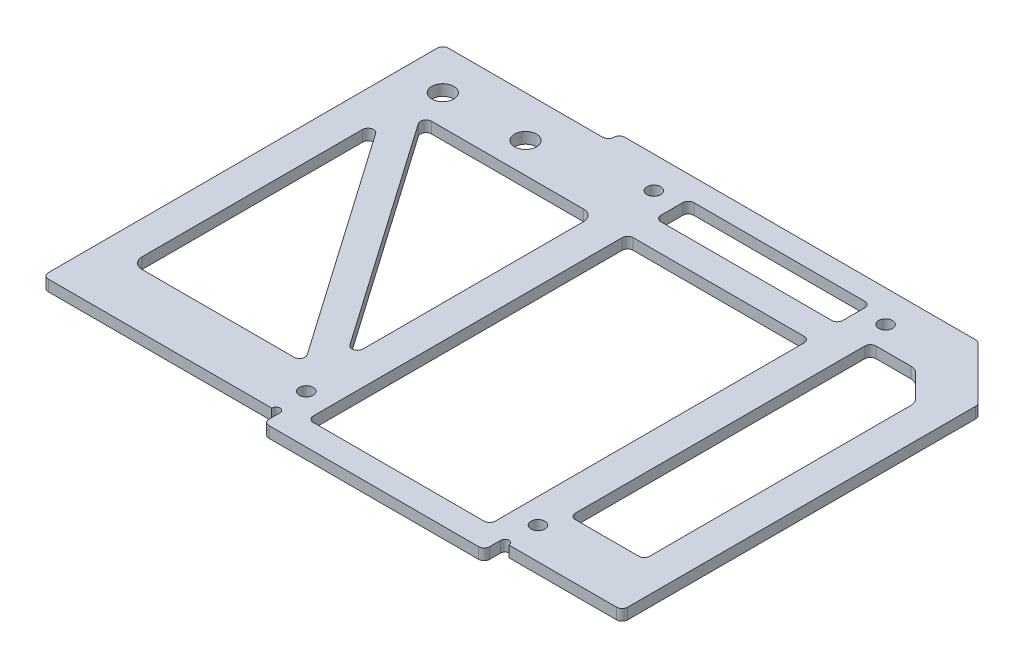
SolidWorks part; units mm, degrees
material "Thornel Mat VMA"
ref_plane "前视基准面" through (0, 0, 0) normal (0, 0, 1) x (1, 0, 0)
ref_plane "上视基准面" through (0, 0, 0) normal (0, 1, 0) x (1, 0, 0)
ref_plane "右视基准面" through (0, 0, 0) normal (1, 0, 0) x (0, 0, -1)
sketch "草图1" plane through (0, 0, 0) normal (0, 1, 0) x (1, 0, 0)
  line L0 (7.5, -7.5) -> (22.5, -7.5) construction
  line L1 (0, 0) -> (30, 0)
  line L2 (0, 0) -> (0, -72.5)
  line L3 (0, -72.5) -> (43, -72.5)
  line L4 (105, -8) -> (105, -72.5)
  line L5 (83, -72.5) -> (105, -72.5)
  line L6 (15, -28) -> (43, -28) construction
  line L11 (30, 0) -> (30, 2)
  line L12 (30, 2) -> (95, 2)
  line L15 (43, -72.5) -> (43, -75.5)
  line L16 (43, -75.5) -> (83, -75.5)
  line L17 (83, -72.5) -> (83, -75.5)
  line L18 (95, 2) -> (105, -8)
  line L19 (42, -3.75) -> (84, -3.75) construction
  line L20 (42, -3.75) -> (42, -66.75) construction
  line L21 (42, -66.75) -> (84, -66.75) construction
  line L22 (84, -3.75) -> (84, -66.75) construction
  line L23 (63, -66.75) -> (63, -75.5) construction
  circle A0 centre (7.5, -7.5) radius 2
  circle A1 centre (22.5, -7.5) radius 2
  circle A2 centre (15, -28) radius 1.5 construction
  circle A5 centre (43, -28) radius 1.5 construction
  circle A6 centre (42, -3.75) radius 1.25
  circle A7 centre (42, -66.75) radius 1.25
  circle A8 centre (84, -66.75) radius 1.25
  circle A9 centre (84, -3.75) radius 1.25
  dimension "D4" = 4
  dimension "D5" = 7.5
  dimension "D6" = 7.5
  dimension "D11" = 3
  dimension "D12" = 30
  dimension "D10" = 15
  dimension "D20" = 2.5
  dimension "D1" = 72.5
  dimension "D2" = 65
  dimension "D3" = 15
  dimension "D7" = 43
  dimension "D8" = 28
  dimension "D9" = 28
  dimension "D13" = 2
  dimension "D14" = 3
  dimension "D15" = 40
  dimension "D16" = 135
  dimension "D17" = 105
  dimension "D18" = 42
  dimension "D19" = 63
  dimension "D21" = 5.75
extrude "凸台-拉伸1" add sketch "草图1" along normal blind 2
sketch "草图3" plane through (0, 2, 0) normal (0, 1, 0) x (1, 0, 0)
  line L0 (46.5, -8) -> (46.5, -2)
  line L5 (79.5, -8) -> (46.5, -8)
  line L9 (46.5, -2) -> (79.5, -2)
  line L10 (79.5, -2) -> (79.5, -8)
  line L12 (46.5, -13) -> (79.5, -13)
  line L13 (46.5, -13) -> (46.5, -71)
  line L14 (46.5, -71) -> (79.5, -71)
  line L15 (79.5, -71) -> (79.5, -13)
  line L22 (43, -75.5) -> (83, -75.5) construction
  line L23 (95, 2) -> (30, 2) construction
  line L25 (95, 2) -> (30, 2) construction
  line L27 (6, -13) -> (40.5, -13)
  line L28 (6, -13) -> (6, -62.5)
  line L29 (6, -62.5) -> (40.5, -62.5)
  line L30 (40.5, -13) -> (40.5, -62.5)
  line L31 (0, -72.5) -> (43, -72.5) construction
  line L32 (0, 0) -> (0, -72.5) construction
  line L33 (93.6863, -8) -> (99, -13.3137)
  line L34 (85.5, -8) -> (93.6863, -8)
  line L35 (85.5, -8) -> (85.5, -62.5)
  line L36 (85.5, -62.5) -> (99, -62.5)
  line L37 (99, -13.3137) -> (99, -62.5)
  line L38 (105, -72.5) -> (105, -8) construction
  line L39 (105, -8) -> (95, 2) construction
  circle A0 centre (42, -66.75) radius 1.25 construction
  circle A1 centre (84, -66.75) radius 1.25 construction
  dimension "D1" = 4.5
  dimension "D2" = 4.5
  dimension "D3" = 4.5
  dimension "D4" = 15
  dimension "D5" = 4
  dimension "D6" = 6
  dimension "D7" = 6
  dimension "D8" = 10
  dimension "D9" = 6
  dimension "D10" = 6
  dimension "D11" = 6
  dimension "D12" = 10
  dimension "D13" = 8
extrude "切除-拉伸2" cut sketch "草图3" against normal through all
sketch "草图2" plane through (0, 2, 0) normal (0, 1, 0) x (1, 0, 0)
  line L15 (0, -72.5) -> (43, -72.5) construction
  line L16 (83, -72.5) -> (105, -72.5) construction
  circle A2 centre (42.25, -72.5) radius 0.75
  circle A3 centre (83.75, -72.5) radius 0.75
  dimension "D11" = 1.5
extrude "切除-拉伸1" cut sketch "草图2" against normal through all
sketch "草图4" plane through (0, 2, 0) normal (0, 1, 0) x (1, 0, 0)
  line L1 (6, -13) -> (40.5, -62.5)
extrude "拉伸-薄壁1" add sketch "草图4" against normal up to surface (2 mm away) thin up to face at (92.5373, 0, 30.8627) thin type mid plane wall 5
fillet "圆角1" radius 1 24 edges at (0, 1, 0) (83, 1, 75.5) (0, 1, 72.5) (43, 1, 75.5) (105, 1, 72.5) (30, 1, -2) (30, 1, 0) (105, 1, 8) (95, 1, -2) (46.5, 1, 71) (46.5, 1, 13) (79.5, 1, 13) (79.5, 1, 71) (46.5, 1, 8) (46.5, 1, 2) (79.5, 1, 2) (79.5, 1, 8) (99, 1, 62.5) (85.5, 1, 62.5) (85.5, 1, 8) (37.4527, 1, 62.5) (40.5, 1, 58.1278) (6, 1, 17.3722) (9.0473, 1, 13)
fillet "圆角2" radius 2 4 edges at (93.6863, 1, 8) (99, 1, 13.3137) (6, 1, 62.5) (40.5, 1, 13)
